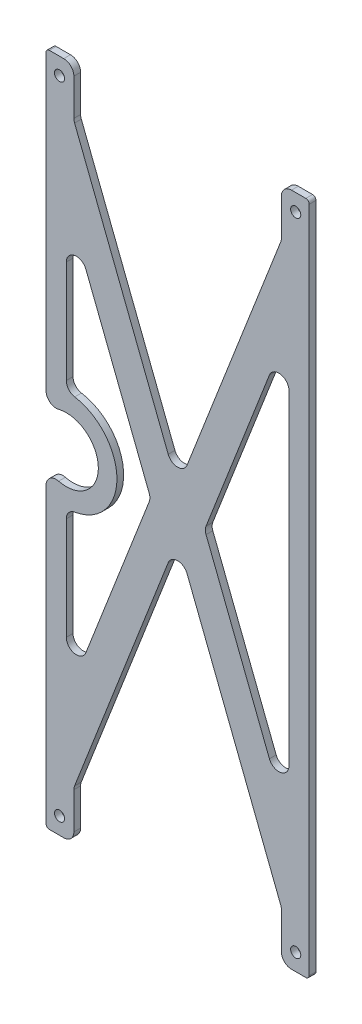
SolidWorks part; units mm, degrees
ref_plane "前视基准面" through (0, 0, 0) normal (0, 0, 1) x (1, 0, 0)
ref_plane "上视基准面" through (0, 0, 0) normal (0, 1, 0) x (1, 0, 0)
ref_plane "右视基准面" through (0, 0, 0) normal (1, 0, 0) x (0, 0, -1)
sketch "草图1" plane through (0, 0, 0) normal (0, 0, 1) x (1, 0, 0)
  line L0 (-433.5341, 0) -> (21243.1718, 0) construction
  line L1 (0, -433.5341) -> (0, 21243.1718) construction
  line L2 (-31, -100) -> (39, 79.4872)
  line L3 (-39, -100) -> (39, -100)
  line L4 (-39, -100) -> (-39, 100)
  line L5 (-39, 100) -> (39, 100)
  line L6 (39, -100) -> (39, 100)
  line L7 (-39, -100) -> (39, 100) construction
  line L8 (-39, 100) -> (39, -100) construction
  line L25 (31, -100) -> (-39, 79.4872)
  line L26 (-31, 100) -> (39, -79.4872)
  line L27 (31, 100) -> (-39, -79.4872)
  line L28 (-35, -1030.2665) -> (-35, 48969.7335) construction
  line L29 (35, -1030.2665) -> (35, 48969.7335) construction
  line L30 (33, 64.1026) -> (33, -64.1026)
  line L31 (-33, 64.1026) -> (-33, -64.1026)
  point P4 (0, 0)
  dimension "D1" = 8
  dimension "D2" = 35
  dimension "D3" = 4
  dimension "D4" = 200
  dimension "D5" = 6
extrude "凸台-拉伸1" add sketch "草图1" along normal blind 2 contours L6 | L26 L2 L25 L3 L6 | L25 L27 L4 L3 L2 | L4 | L31 L25 L4 L27 | L2 L30 L26 L6 | L26 L27 L25 L2 | L5 L27 L26 L2 L6 | L27 L26 L5 L4 L25 | L4 | L6 region at (20.5202, 52.6159, 0) region at (36.1071, 0, 0) region at (20.5202, -52.6159, 0) region at (0, 0, 0) region at (-20.5202, -52.6159, 0) region at (-20.5202, 52.6159, 0) region at (-36.1071, 0, 0)
sketch "草图4" plane through (0, 0, 2) normal (0, 0, 1) x (1, 0, 0)
  line L0 (-39, -100) -> (-39, 100) construction
  line L1 (-39, 100) -> (-31, 100) construction
  line L2 (0, -1000) -> (0, 49000) construction
  line L4 (-754.3874, 0) -> (42673.3512, 0) construction
  circle A0 centre (-35, 95) radius 1.5
  circle A1 centre (-35, -95) radius 1.5
  circle A2 centre (35, -95) radius 1.5
  circle A3 centre (35, 95) radius 1.5
  dimension "D1" = 3
  dimension "D2" = 4
  dimension "D3" = 5
extrude "切除-拉伸3" cut sketch "草图4" against normal through all
fillet "圆角4" radius 1 8 edges at (39, -100, 1) (31, -100, 1) (-31, -100, 1) (-39, -100, 1) (31, 100, 1) (39, 100, 1) (-31, 100, 1) (-39, 100, 1)
sketch "草图6" plane through (0, 0, 2) normal (0, 0, 1) x (1, 0, 0)
  line L0 (-30.7517, -99.3633) -> (0, -20.5128) construction
  line L1 (30.7517, -99.3633) -> (0, -20.5128) construction
  line L2 (30.7517, 99.3633) -> (0, 20.5128) construction
  line L3 (-30.7517, 99.3633) -> (0, 20.5128) construction
  line L4 (-30.7517, -99.3633) -> (0, -20.5128)
  line L5 (30.7517, -99.3633) -> (0, -20.5128)
  line L6 (30.7517, 99.3633) -> (0, 20.5128)
  line L7 (-30.7517, 99.3633) -> (0, 20.5128)
  line L9 (-35.41, -97.5466) -> (0, -6.7518)
  line L10 (35.41, -97.5466) -> (0, -6.7518)
  line L11 (35.41, 97.5466) -> (0, 6.7518)
  line L12 (-35.41, 97.5466) -> (0, 6.7518)
  line L15 (-1000, 0) -> (49000, 0) construction
  line L16 (-30.7517, -99.3633) -> (-30.7517, -85.6023)
  line L17 (0, -1000) -> (0, 49000) construction
  line L18 (30.7517, -99.3633) -> (30.7517, -85.6023)
  line L19 (-30.7517, 99.3633) -> (-30.7517, 85.6023)
  line L20 (30.7517, 99.3633) -> (30.7517, 85.6023)
  line M22 (0, 20.5128) -> (-30.7517, 99.3633)
  line M31 (0, -20.5128) -> (30.7517, -99.3633)
  dimension "D1" = 5
extrude "切除-拉伸5" cut sketch "草图6" against normal through all contours L20 L6 L19 L12 L11 M22 | L18 L10 L9 L16 L4 M31 region at (-29.64, -92.4828, 2) region at (29.64, 92.4828, 2)
fillet "圆角7" radius 3 16 edges at (30.7517, 85.6023, 1) (0, 6.7518, 1) (-30.7517, 85.6023, 1) (-30.7517, 99.3633, 1) (-30.7517, -99.3633, 1) (0, -6.7518, 1) (30.7517, -85.6023, 1) (30.7517, -99.3633, 1) (30.7517, 99.3633, 1) (33, 64.1026, 1) (33, -64.1026, 1) (8, 0, 1) (-8, 0, 1) (-33, -64.1026, 1) (-33, 64.1026, 1) (-30.7517, -85.6023, 1)
sketch "草图7" plane through (0, 0, 2) normal (0, 0, 1) x (1, 0, 0)
  line L0 (-33, 48.1536) -> (-33, -48.1536) construction
  circle A0 centre (-33, 0) radius 9.5
  circle A1 centre (-33, 0) radius 15
  line M11 (-33, -48.1536) -> (-33, 48.1536)
  line M23 (-39, 99) -> (-39, -99)
  dimension "D1" = 19
  dimension "D2" = 30
extrude "凸台-拉伸2" add sketch "草图7" against normal through all contours A1 A0 M11 region at (-26.0453, 6.9547, 2)
extrude "切除-拉伸6" cut sketch "草图7<4>" against normal through all contours A0 M11 M23 region at (-35.8823, 0, 2)
sketch "草图7<4>" plane through (0, 0, 2) normal (0, 0, 1) x (1, 0, 0) same geometry as "草图7"
fillet "圆角8" radius 3 4 edges at (-39, 7.3655, 1) (-39, -7.3655, 1) (-33, -15, 1) (-33, 15, 1)
